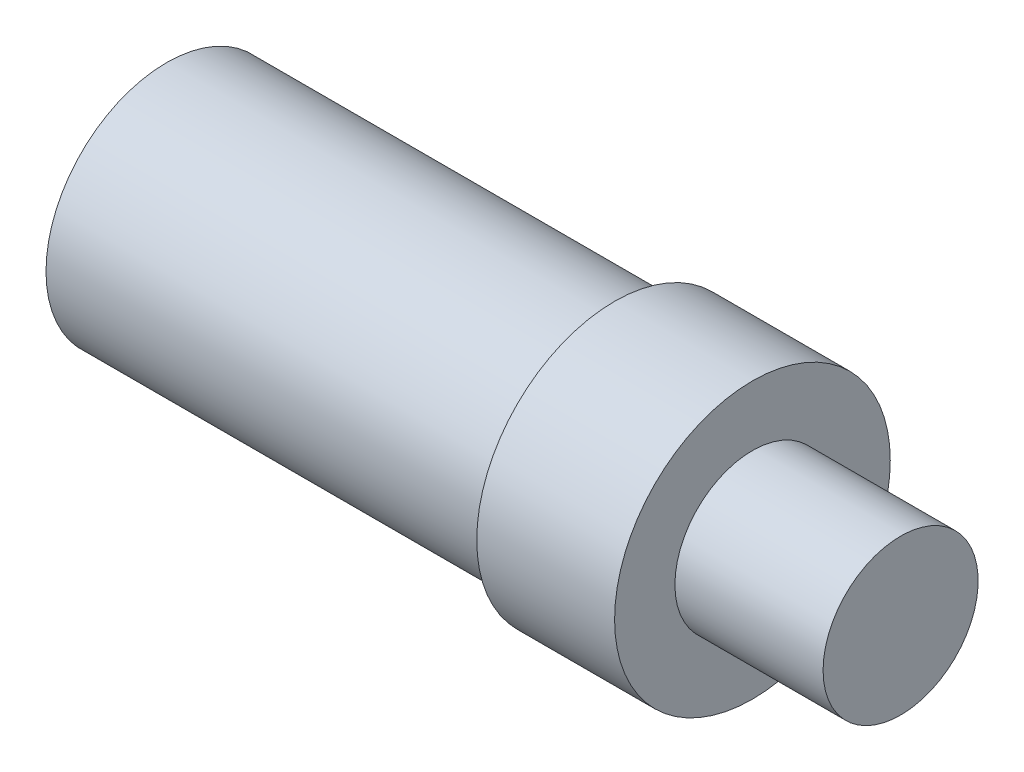
SolidWorks part; units mm, degrees
ref_plane "Front Plane" through (0, 0, 0) normal (0, 0, 1) x (1, 0, 0)
ref_plane "Top Plane" through (0, 0, 0) normal (0, 1, 0) x (1, 0, 0)
ref_plane "Right Plane" through (0, 0, 0) normal (1, 0, 0) x (0, 0, -1)
sketch "Torch_Plug Sketch" plane through (0, 0, 0) normal (0, 0, 1) x (1, 0, 0)
  line L0 (-300, 0) -> (300, 0) construction
  line L1 (-33.4, 0) -> (-33.4, 4.5)
  line L2 (-33.4, 4.5) -> (-42, 4.5)
  line L3 (-42, 4.5) -> (-42, 8)
  line L4 (-42, 8) -> (-50, 8)
  line L5 (-50, 8) -> (-50, 7)
  line L6 (-50, 7) -> (-76, 7)
  line L7 (-76, 7) -> (-76, 0)
  line L8 (-76, 0) -> (-33.4, 0)
revolve "Torch_Plug" add sketch "Torch_Plug Sketch" angle 360 about L0
ref_axis "Engine Axis" through (-31.27, 0, 0) along (-1, 0, 0)
